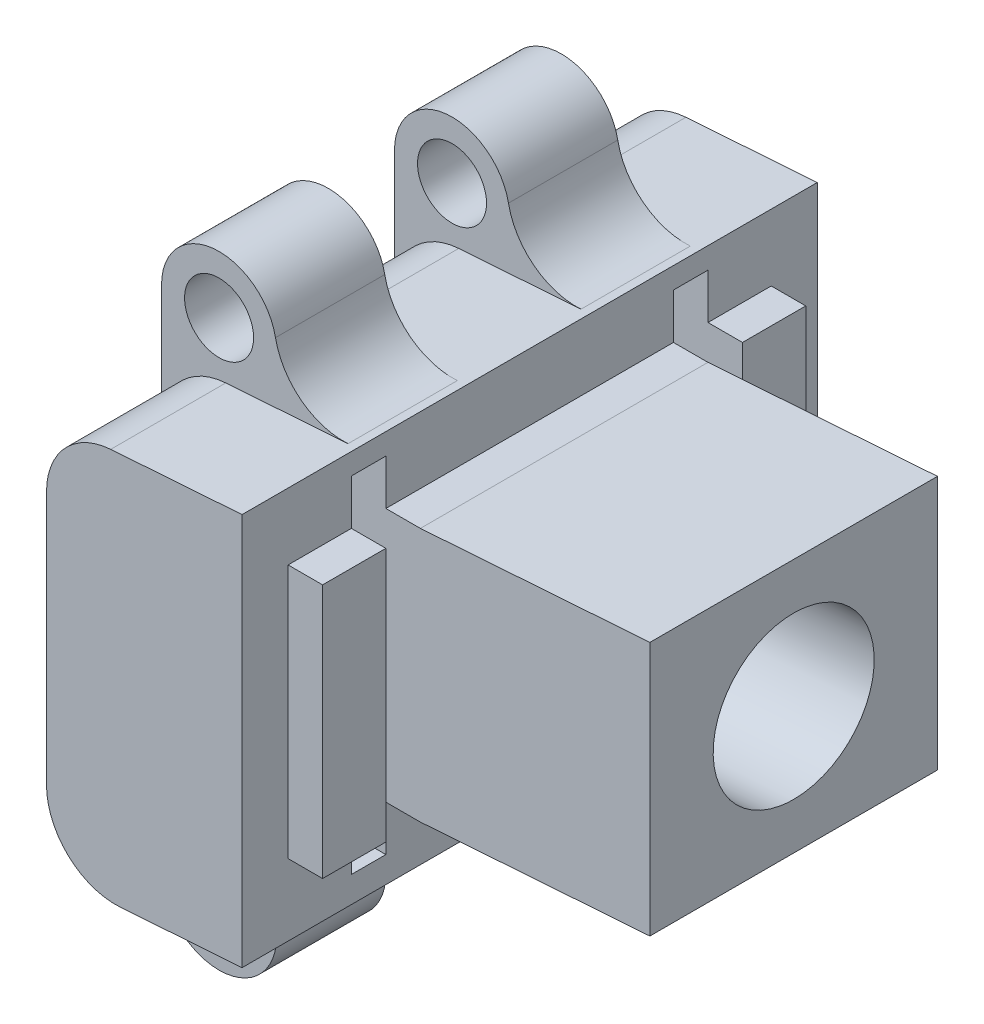
SolidWorks part; units mm, degrees
ref_plane "Front Plane" through (0, 0, 0) normal (0, 0, 1) x (1, 0, 0)
ref_plane "Top Plane" through (0, 0, 0) normal (0, 1, 0) x (1, 0, 0)
ref_plane "Right Plane" through (0, 0, 0) normal (1, 0, 0) x (0, 0, -1)
sketch "Sketch1" plane through (0, 0, 0) normal (1, 0, 0) x (0, 0, -1)
  line L1 (0, 0) -> (50, 0)
  line L2 (0, 0) -> (0, 34.11)
  line L3 (0, 34.11) -> (50, 34.11)
  line L4 (50, 0) -> (50, 34.11)
  dimension "D1" = 50
  dimension "D2" = 34.11
extrude "Boss-Extrude1" add sketch "Sketch1" along normal blind 20
sketch "Sketch2" plane through (0, 0, 0) normal (0, 0, 1) x (1, 0, 0)
  line L0 (3, 37.11) -> (3, 34.11) construction
  line L1 (20, 34.11) -> (0, 34.11) construction
  line L2 (0, 34.11) -> (0, 37.11)
  line L3 (0, 34.11) -> (3, 34.11)
  line L4 (3, 34.11) -> (6, 34.11)
  line L5 (6, 34.11) -> (6, 37.11)
  line L6 (6, 37.11) -> (3, 37.11) construction
  circle A0 centre (3, 37.11) radius 2
  arc A1 (6, 37.11) -> (0, 37.11) centre (3, 37.11) ccw
  dimension "D1" = 4
  dimension "D2" = 3
  dimension "D3" = 3
ref_plane "Plane1" through (0, 0, -10) normal (0, 0, 1) x (1, 0, 0)
sketch "Sketch3" plane through (0, 0, -10) normal (0, 0, 1) x (1, 0, 0)
  line L0 (5, 39.11) -> (5, 34.11) construction
  line L2 (0, 34.11) -> (0, 39.11)
  line L3 (0, 34.11) -> (5, 34.11)
  line L4 (5, 34.11) -> (10, 34.11)
  line L5 (10, 34.11) -> (10, 39.11)
  line L6 (10, 39.11) -> (5, 39.11) construction
  line L7 (0, 34.11) -> (0, 0) construction
  line L8 (20, 34.11) -> (0, 34.11) construction
  circle A0 centre (5, 39.11) radius 3
  arc A1 (10, 39.11) -> (0, 39.11) centre (5, 39.11) ccw
  dimension "D1" = 6
  dimension "D2" = 5
  dimension "D3" = 5
extrude "Boss-Extrude2" add sketch "Sketch3" against normal blind 9.5
pattern_linear "LPattern1" count 2 spacing 20.25 along (0, 0, -1) of "Boss-Extrude2"
ref_plane "Plane2" through (0, 17.055, 0) normal (0, 1, 0) x (1, 0, 0)
mirror "Mirror1" about plane through (0, 17.055, 0) normal (0, 1, 0) of "LPattern1", "Boss-Extrude2"
ref_plane "Plane3" through (0, 0, -25) normal (0, 0, 1) x (1, 0, 0)
sketch "Sketch4" plane through (0, 0, -25) normal (0, 0, 1) x (1, 0, 0)
  line L0 (20, 17.055) -> (0, 17.055) construction
  line L1 (20, 34.11) -> (20, 0) construction
  line L2 (0, 34.11) -> (0, 0) construction
  line L3 (10, 0) -> (10, 34.11) construction
  line L4 (20, 0) -> (0, 0) construction
  line L5 (20, 34.11) -> (0, 34.11) construction
  line L6 (10, 17.055) -> (20, 17.7543) construction
  dimension "D1" = 4
ref_plane "Plane4" through (20, 17.7543, -25) normal (0.9976, 0.0698, 0) x (0, 0, -1)
sketch "Sketch7" plane through (0, 0, 0) normal (0, 0, 1) x (1, 0, 0)
  line L0 (20, 34.11) -> (0, 34.11)
  line L1 (0, 34.11) -> (20, 35.5085)
  line L2 (20, 35.5085) -> (20, 34.11)
  dimension "D1" = 4
extrude "Boss-Extrude3" add sketch "Sketch7" against normal up to surface (50 mm away) up to face at (10, 17.055, -50)
sketch "Sketch8" plane through (0, 0, 0) normal (0, 0, 1) x (1, 0, 0)
  line L0 (0, 0) -> (20, 1.3985)
  line L1 (20, 35.5085) -> (20, 0) construction
  line L2 (20, 1.3985) -> (20, 0)
  line L3 (20, 0) -> (0, 0)
  dimension "D1" = 4
extrude "Cut-Extrude3" cut sketch "Sketch8" against normal blind 10
extrude "Cut-Extrude4" cut sketch "Sketch8<2>" against normal up to surface (30.25 mm away) from surface up to face at (5, -3.75, -30.25) starting at face at (5, -3.75, -19.5)
sketch "Sketch8<2>" plane through (0, 0, 0) normal (0, 0, 1) x (1, 0, 0) same geometry as "Sketch8"
extrude "Cut-Extrude5" cut sketch "Sketch8<3>" along direction (0, 0, 1) on the side against the normal up to surface (50 mm away) from surface up to face at (10, 17.4046, -50) starting at face at (5, -3.75, -39.75)
sketch "Sketch8<3>" plane through (0, 0, 0) normal (0, 0, 1) x (1, 0, 0) same geometry as "Sketch8"
sketch "Sketch9" plane through (0, 0, 0) normal (0, 0, 1) x (1, 0, 0)
  line L0 (20, 1.3985) -> (0, 0) construction
  line L1 (20, 0) -> (20, 1.3985) construction
  line L2 (10, 0) -> (20, 0) construction
  line L3 (20, 1.3985) -> (10, 0.6993)
  line L4 (20, 0) -> (20, 1.3985)
  line L5 (10, 0) -> (20, 0)
  line L6 (10, 0) -> (10, 0.6993)
extrude "Cut-Extrude6" cut sketch "Sketch9" against normal up to surface (50 mm away) up to face at (10, 17.7543, -50)
sketch "Sketch6" plane through (20, 0, 0) normal (1, 0, 0) x (0, 0, -1)
  line L0 (25, 35.5085) -> (25, 18.4535) construction
  line L3 (12.5, 18.4535) -> (37.5, 18.4535)
  line L4 (12.5, 3.4535) -> (12.5, 33.4535)
  line L5 (12.5, 33.4535) -> (9.5, 33.4535)
  line L6 (9.5, 33.4535) -> (9.5, 3.4535)
  line L7 (9.5, 3.4535) -> (12.5, 3.4535)
  line L8 (40.5, 33.4535) -> (40.5, 3.4535)
  line L9 (37.5, 33.4535) -> (40.5, 33.4535)
  line L10 (37.5, 3.4535) -> (37.5, 33.4535)
  line L11 (40.5, 3.4535) -> (37.5, 3.4535)
  line L12 (50, 35.5085) -> (0, 35.5085) construction
  line L13 (25, 18.4535) -> (25, 1.3985) construction
  line L14 (50, 1.3985) -> (0, 1.3985) construction
  point P9 (25, 18.4535)
  point P12 (12.5, 18.4535)
  dimension "D1" = 25
  dimension "D2" = 30
  dimension "D3" = 3
  dimension "D4" = 30
  dimension "D5" = 3
extrude "Cut-Extrude2" cut sketch "Sketch6" against normal blind 10 contours L6 L7 L4 L5 | L11 L8 L9 L10 region at (20, 18.4535, -39) region at (20, 18.4535, -11)
sketch "Sketch10" plane through (20, 0, 0) normal (1, 0, 0) x (0, 0, -1)
  line L0 (50, 35.5085) -> (0, 35.5085) construction
  line L1 (4, 29.5085) -> (46, 29.5085)
  line L2 (4, 29.5085) -> (4, 7.3985)
  line L3 (4, 7.3985) -> (46, 7.3985)
  line L4 (46, 29.5085) -> (46, 7.3985)
  line L5 (50, 1.3985) -> (50, 35.5085) construction
  line L6 (50, 1.3985) -> (0, 1.3985) construction
  line L7 (0, 35.5085) -> (0, 1.3985) construction
  line L9 (0, 35.5085) -> (50, 35.5085)
  line L10 (0, 35.5085) -> (0, 1.3985)
  line L11 (0, 1.3985) -> (50, 1.3985)
  line L12 (50, 35.5085) -> (50, 1.3985)
  dimension "D1" = 6
  dimension "D2" = 4
  dimension "D3" = 6
  dimension "D4" = 4
extrude "Cut-Extrude7" cut sketch "Sketch10" against normal blind 3
sketch "Sketch11" plane through (0, 1.3985, 0) normal (0, 1, 0) x (1, 0, 0)
  line L1 (20, 50) -> (17, 50)
  line L2 (20, 50) -> (20, 0)
  line L3 (20, 0) -> (17, 0)
  line L4 (17, 50) -> (17, 0)
extrude "Cut-Extrude8" cut sketch "Sketch11" against normal up to surface up to face at (6.6667, 0.4662, -24.9167)
fillet "Fillet1" radius 6 10 edges at (10, 0.6993, -14.75) (10, 0.6993, -35) (10, 34.8093, -35) (10, 34.8093, -14.75) (0, 0, -5) (0, 0, -24.875) (0, 0, -44.875) (0, 34.11, -44.875) (0, 34.11, -24.875) (0, 34.11, -5)
sketch "Sketch5" plane through (20, 17.7543, -25) normal (0.9976, 0.0698, 0) x (0, 0, -1)
  line L1 (0, 17.711) -> (0, 0.6976) construction
  line L6 (25, 17.711) -> (-25, 17.711) construction
  line L10 (0, 0.6976) -> (0, -16.3159) construction
  line L11 (25, -16.3159) -> (-25, -16.3159) construction
  circle A0 centre (0, 0.6976) radius 7
  point P7 (0, 0.6976)
  dimension "D1" = 14
extrude "Cut-Extrude1" cut sketch "Sketch5" against normal blind 10 and the other way up to next
sketch "Sketch13" plane through (20, 0, 0) normal (1, 0, 0) x (0, 0, -1)
  line L0 (37.5, 3.4535) -> (37.5, 33.4535) construction
  line L1 (12.5, 7.3985) -> (37.5, 7.3985) construction
  line L2 (12.5, 3.4535) -> (12.5, 33.4535) construction
  line L3 (37.5, 29.5085) -> (12.5, 29.5085) construction
  line L4 (37.5, 7.3985) -> (37.5, 29.5085)
  line L5 (12.5, 7.3985) -> (37.5, 7.3985)
  line L6 (12.5, 7.3985) -> (12.5, 29.5085)
  line L7 (37.5, 29.5085) -> (12.5, 29.5085)
  ellipse E0 centre (25, 18.4535) end of major axis (25, 11.4364) minor radius 7 construction
  ellipse E1 centre (25, 18.4535) end of major axis (25, 11.4364) minor radius 7
extrude "Boss-Extrude4" add sketch "Sketch13" along direction (0.9976, 0.0698, 0) on the side of the normal blind 20
